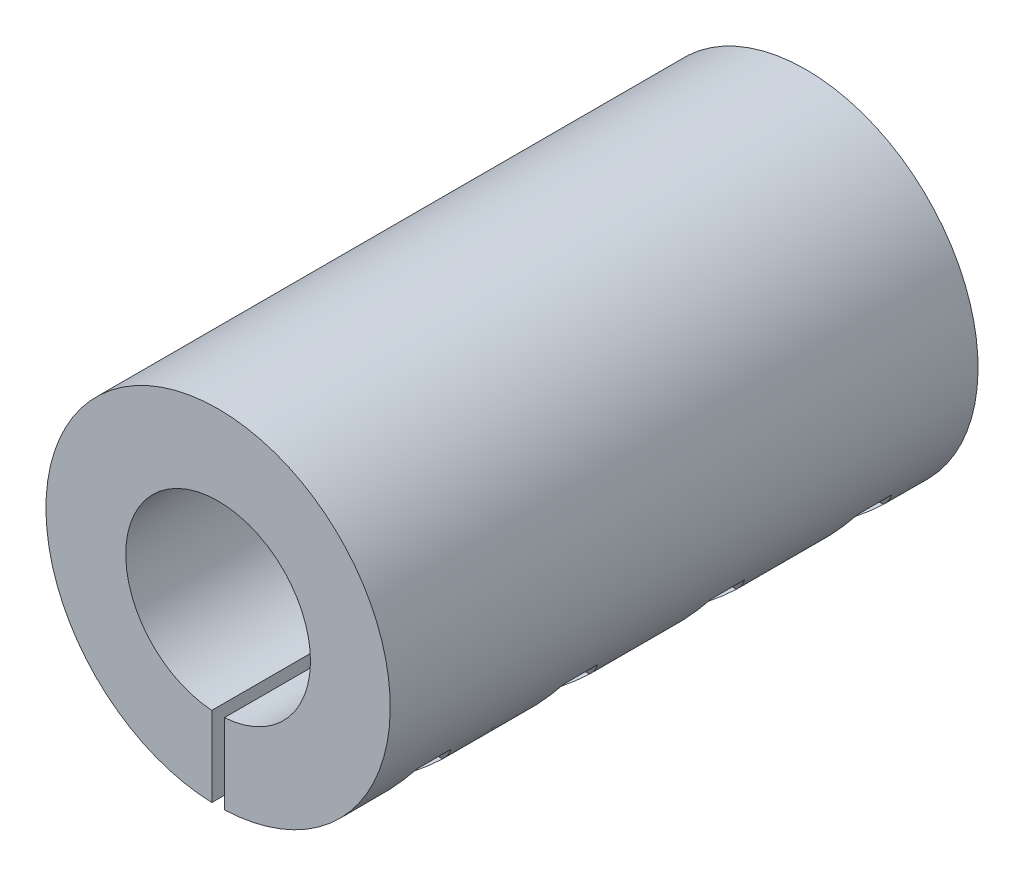
SolidWorks part; units mm, degrees
ref_plane "Front Plane" through (0, 0, 0) normal (0, 0, 1) x (1, 0, 0)
ref_plane "Top Plane" through (0, 0, 0) normal (0, 1, 0) x (1, 0, 0)
ref_plane "Right Plane" through (0, 0, 0) normal (1, 0, 0) x (0, 0, -1)
sketch "Sketch1" plane through (0, 0, 0) normal (0, 0, 1) x (1, 0, 0)
  circle A0 centre (0, 0) radius 11.5
  circle A1 centre (0, 0) radius 20.5
  dimension "D1" = 23
  dimension "D2" = 41
extrude "Boss-Extrude1" add sketch "Sketch1" along normal blind 35
sketch "Sketch2" plane through (0, 0, 35) normal (0, 0, 1) x (1, 0, 0)
  circle A0 centre (0, 0) radius 11
  circle A1 centre (0, 0) radius 20.5
  dimension "D1" = 22
extrude "Boss-Extrude2" add sketch "Sketch2" along normal blind 35
sketch "Sketch3" plane through (0, 0, 0) normal (0, 0, -1) x (-1, 0, 0)
  line L1 (-0.75, 0) -> (0.75, 0)
  line L2 (-0.75, 0) -> (-0.75, -20.5)
  line L3 (-0.75, -20.5) -> (0.75, -20.5)
  line L4 (0.75, 0) -> (0.75, -20.5)
  line L5 (-0.75, 0) -> (0.75, -20.5) construction
  line L6 (-0.75, -20.5) -> (0.75, 0) construction
  circle A0 centre (0, 0) radius 20.5 construction
  point P0 (0, -10.25)
  point P8 (0, 0)
  dimension "D1" = 1.5
extrude "Cut-Extrude1" cut sketch "Sketch3" against normal up to surface (70 mm away) up to face at (20.5, 0, 70)
ref_plane "Plane1" through (4, 0, 0) normal (1, 0, 0) x (0, 0, -1)
ref_plane "Plane2" through (-4, 0, 0) normal (1, 0, 0) x (0, 0, -1)
sketch "Sketch4" plane through (0, 0, 0) normal (1, 0, 0) x (0, 0, -1)
  line L1 (-70, -18.3955) -> (-52.5, -18.3955) construction
  line L2 (0, -11.4755) -> (-35, -11.4755) construction
  line L4 (-70, 20.5) -> (-70, -20.4863) construction
  line L5 (-52.5, -18.3955) -> (-35, -18.3955) construction
  line L7 (-35, -18.3955) -> (-17.5, -18.3955) construction
  line L8 (-17.5, -18.3955) -> (0, -18.3955) construction
  line L9 (0, -20.4863) -> (0, 20.5) construction
  circle A0 centre (-61.25, -14.9755) radius 2
  circle A1 centre (-8.75, -14.9755) radius 2
  circle A2 centre (-43.75, -14.9755) radius 2
  circle A3 centre (-26.25, -14.9755) radius 2
  point P8 (-61.25, -18.3955)
  point P15 (-8.75, -18.3955)
  point P19 (0, 0)
  point P20 (-43.75, -18.3955)
  point P21 (0, 0)
  point P24 (-26.25, -18.3955)
  point P25 (0, 0)
  dimension "D1" = 4
  dimension "D2" = 3.5
extrude "Cut-Extrude2" cut sketch "Sketch4" against normal up to surface and the other way up to surface up to face at (0, 0.0069, 35) other way up to face at (0, 0.0069, 35)
sketch "Sketch6" plane through (4, 0, 0) normal (1, 0, 0) x (0, 0, -1)
  line L1 (-57.2663, -14.9755) -> (-59.2581, -11.5255)
  line L2 (-59.2581, -11.5255) -> (-63.2419, -11.5255)
  line L3 (-63.2419, -11.5255) -> (-65.2337, -14.9755)
  line L4 (-65.2337, -14.9755) -> (-63.2419, -18.4255)
  line L5 (-63.2419, -18.4255) -> (-59.2581, -18.4255)
  line L6 (-59.2581, -18.4255) -> (-57.2663, -14.9755)
  line L7 (-4.7663, -14.9755) -> (-6.7581, -11.5255)
  line L8 (-6.7581, -11.5255) -> (-10.7419, -11.5255)
  line L9 (-10.7419, -11.5255) -> (-12.7337, -14.9755)
  line L10 (-12.7337, -14.9755) -> (-10.7419, -18.4255)
  line L11 (-10.7419, -18.4255) -> (-6.7581, -18.4255)
  line L12 (-6.7581, -18.4255) -> (-4.7663, -14.9755)
  line L13 (-39.7663, -14.9755) -> (-41.7581, -11.5255)
  line L14 (-41.7581, -11.5255) -> (-45.7419, -11.5255)
  line L15 (-45.7419, -11.5255) -> (-47.7337, -14.9755)
  line L16 (-47.7337, -14.9755) -> (-45.7419, -18.4255)
  line L17 (-45.7419, -18.4255) -> (-41.7581, -18.4255)
  line L18 (-41.7581, -18.4255) -> (-39.7663, -14.9755)
  line L19 (-22.2663, -14.9755) -> (-24.2581, -11.5255)
  line L20 (-24.2581, -11.5255) -> (-28.2419, -11.5255)
  line L21 (-28.2419, -11.5255) -> (-30.2337, -14.9755)
  line L22 (-30.2337, -14.9755) -> (-28.2419, -18.4255)
  line L23 (-28.2419, -18.4255) -> (-24.2581, -18.4255)
  line L24 (-24.2581, -18.4255) -> (-22.2663, -14.9755)
  circle A0 centre (-61.25, -14.9755) radius 3.45 construction
  circle A1 centre (-8.75, -14.9755) radius 3.45 construction
  circle A2 centre (-43.75, -14.9755) radius 3.45 construction
  circle A3 centre (-26.25, -14.9755) radius 3.45 construction
  dimension "D1" = 6.9
extrude "Cut-Extrude3" cut sketch "Sketch6" along normal up to surface (4.9861 mm away) up to face at (-13.9501, -15.0215, 63.2495)
sketch "Sketch7" plane through (-4, 0, 0) normal (1, 0, 0) x (0, 0, -1)
  circle A0 centre (-61.25, -14.9755) radius 3.6
  circle A1 centre (-8.75, -14.9755) radius 3.6
  circle A2 centre (-43.75, -14.9755) radius 3.6
  circle A3 centre (-26.25, -14.9755) radius 3.6
  dimension "D1" = 7.2
extrude "Cut-Extrude4" cut sketch "Sketch7" against normal up to surface (9.9994 mm away) up to face at (13.3878, -15.0652, 26.25)
